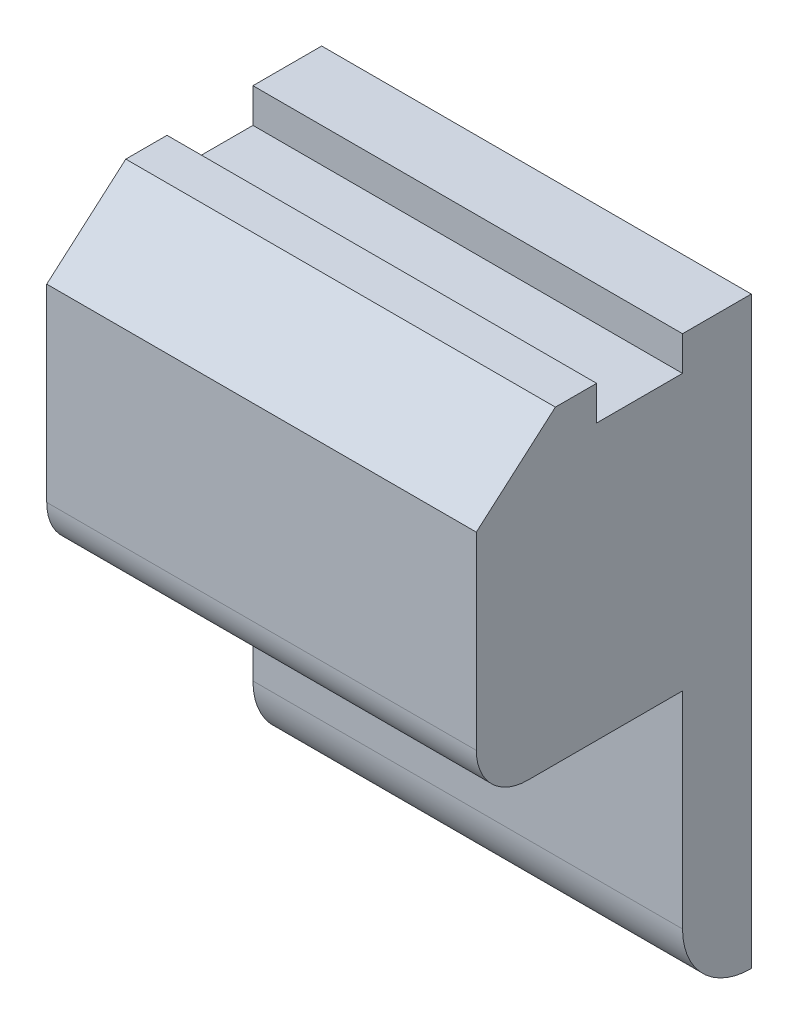
SolidWorks part; units mm, degrees
ref_plane "Front" through (0, 0, 0) normal (0, 0, 1) x (1, 0, 0)
ref_plane "Top" through (0, 0, 0) normal (0, 1, 0) x (1, 0, 0)
ref_plane "Right" through (0, 0, 0) normal (1, 0, 0) x (0, 0, -1)
sketch "Sketch1" plane through (0, 0, 0) normal (0, 1, 0) x (1, 0, 0)
  circle A0 centre (0, 0) radius 4.25 construction
  circle A1 centre (0, 0) radius 4.4
  circle A2 centre (0, 0) radius 6.4
  dimension "D1" = 8.5
  dimension "D3" = 2
  dimension "D2" = 0.15
extrude "Boss-Extrude1" add sketch "Sketch1" along normal blind 10
ref_plane "Plane1" through (0, -3, 0) normal (0, -1, 0) x (-1, 0, 0)
chamfer "Chamfer1" distance 1 angle 10 1 edges at (0, 10, 4.4) first distance on face at (0, 10, 6.4)
sketch "Sketch2" plane through (0, 0, 0) normal (0, -1, 0) x (1, 0, 0)
  circle A0 centre (0, 0) radius 6.4
  circle A1 centre (0, 0) radius 6.4 construction
sketch "Sketch3" plane through (0, -3, 0) normal (0, -1, 0) x (-1, 0, 0)
  line L1 (6.25, 8.5) -> (-6.25, 8.5)
  line L2 (6.25, 8.5) -> (6.25, -8.5)
  line L3 (6.25, -8.5) -> (-6.25, -8.5)
  line L4 (-6.25, 8.5) -> (-6.25, -8.5)
  line L5 (0, -8.5) -> (0, 8.5) construction
  line L6 (6.25, 0) -> (-6.25, 0) construction
  point P0 (0, 0)
  dimension "D1" = 17
  dimension "D2" = 12.5
loft "Loft1" add profiles "Sketch2", "Sketch3" connector at (0, 0, -6.4) connector at (-6.25, -3, -8.5)
sketch "Sketch4" plane through (0, 0, 0) normal (1, 0, 0) x (0, 0, -1)
  line L0 (-8.5, -3) -> (-8.5, -6)
  line L1 (8.5, -3) -> (8.5, -7.493)
  line L2 (8.5, -7.493) -> (-1.2357, -62.493)
  line L3 (-8.5, -6) -> (-18.5, -62.493)
  line L5 (-8.5, -3) -> (8.5, -3)
  line L7 (-1.2357, -62.493) -> (-4.2449, -79.493)
  line L8 (-4.2449, -79.493) -> (-68.5, -79.493)
  line L9 (-68.5, -79.493) -> (-68.5, -62.493)
  line L10 (-68.5, -62.493) -> (-18.5, -62.493)
  dimension "D1" = 3
  dimension "D2" = 17
  dimension "D3" = 10
  dimension "D4" = 55
  dimension "D5" = 17
  dimension "D6" = 60
extrude "Boss-Extrude2" add sketch "Sketch4" along normal mid plane 12.5 contours L10 L9 L8 L7 | L2 L1 L5 L0 L3 region at (0, -4.0854, 0)
sketch "Sketch5" plane through (0, 0, 0) normal (-1, 0, 0) x (0, 0, 1)
  line L8 (6.5, -5) -> (-6.5, -5)
  line L13 (6.5, -5) -> (-6.5, -5)
  line L17 (66.5, -64.493) -> (16.8229, -64.493)
  line L21 (16.8229, -64.493) -> (6.5, -6.1756)
  line L22 (6.5, -6.1756) -> (6.5, -5)
  line L24 (-6.5, -5) -> (-6.5, -7.3174)
  line L25 (-6.5, -7.3174) -> (5.922, -77.493)
  line L26 (5.922, -77.493) -> (66.5, -77.493)
  line L27 (66.5, -77.493) -> (66.5, -64.493)
  line L28 (66.5, -64.493) -> (16.8229, -64.493)
  line L29 (16.8229, -64.493) -> (6.5, -6.1756)
  line L30 (6.5, -6.1756) -> (6.5, -5)
  line L32 (-6.5, -5) -> (-6.5, -7.3174)
  line L33 (-6.5, -7.3174) -> (5.922, -77.493)
  line L34 (5.922, -77.493) -> (66.5, -77.493)
  line L35 (66.5, -77.493) -> (66.5, -64.493)
  dimension "D1" = 2
extrude "Cut-Extrude1" cut sketch "Sketch5" against normal blind 5 from surface starting at face at (-6.25, -37.4648, 21.0306)
extrude "Cut-Extrude2" cut sketch "Sketch5<2>" along normal blind 5 from surface starting at face at (6.25, -37.4648, 18.9056)
sketch "Sketch5<2>" plane through (0, 0, 0) normal (-1, 0, 0) x (0, 0, 1) same geometry as "Sketch5"
fillet "Fillet23" radius 1 16 edges at (-1.25, -5.5878, 6.5) (-1.25, -35.3343, 11.6615) (-1.25, -64.493, 41.6615) (-1.25, -70.993, 66.5) (-1.25, -77.493, 36.211) (-1.25, -42.4052, -0.289) (-1.25, -6.1587, -6.5) (-1.25, -5, 0) (1.25, -5.5878, 6.5) (1.25, -5, 0) (1.25, -6.1587, -6.5) (1.25, -42.4052, -0.289) (1.25, -77.493, 36.211) (1.25, -70.993, 66.5) (1.25, -64.493, 41.6615) (1.25, -35.3343, 11.6615)
sketch "Sketch6" plane through (0, 0, 0) normal (1, 0, 0) x (0, 0, -1)
  line L8 (-68.5, -63.493) -> (-71, -63.493)
  line L9 (-68.5, -79.493) -> (-68.5, -62.493) construction
  line L10 (-71, -63.493) -> (-71, -62.493)
  line L11 (-71, -62.493) -> (-72.2, -62.493)
  line L12 (-72.2, -62.493) -> (-74.5, -64.493)
  line L13 (-74.5, -64.493) -> (-74.5, -69.993)
  line L14 (-73, -71.493) -> (-68.5, -71.493)
  line L15 (-68.5, -71.493) -> (-68.5, -63.493)
  arc A0 (-74.5, -69.993) -> (-73, -71.493) centre (-73, -69.993) ccw
  dimension "D4" = 1.5
  dimension "D1" = 2
  dimension "D2" = 2.3
  dimension "D3" = 8
  dimension "D7" = 2.5
  dimension "D8" = 1
  dimension "D9" = 1.2
extrude "Boss-Extrude3" add sketch "Sketch6" along normal mid plane 12.5
fillet "Fillet30" radius 2 5 edges at (0, -62.493, 18.5) (0, -7.493, -8.5) (0, -79.493, 4.2449) (0, -79.493, 68.5) (0, -6, 8.5)
fillet "Fillet36" radius 2 1 edges
fillet "Fillet37" radius 2 1 edges
sketch "Sketch7" plane through (0, 0, 0) normal (1, 0, 0) x (0, 0, -1)
  line L0 (-66.5, -77.493) -> (-66.5, -64.493) construction
  line L1 (-66.5, -88.7612) -> (8.5, -88.7612)
  line L2 (-66.5, -88.7612) -> (-66.5, 10)
  line L3 (-66.5, 10) -> (8.5, 10)
  line L4 (8.5, -88.7612) -> (8.5, 10)
  line L5 (8.5, -3.9316) -> (8.5, -7.3174) construction
  line L6 (5.4, 10) -> (-5.4, 10) construction
extrude "Cut-Extrude3" cut sketch "Sketch7" against normal through all both and the other way through all
